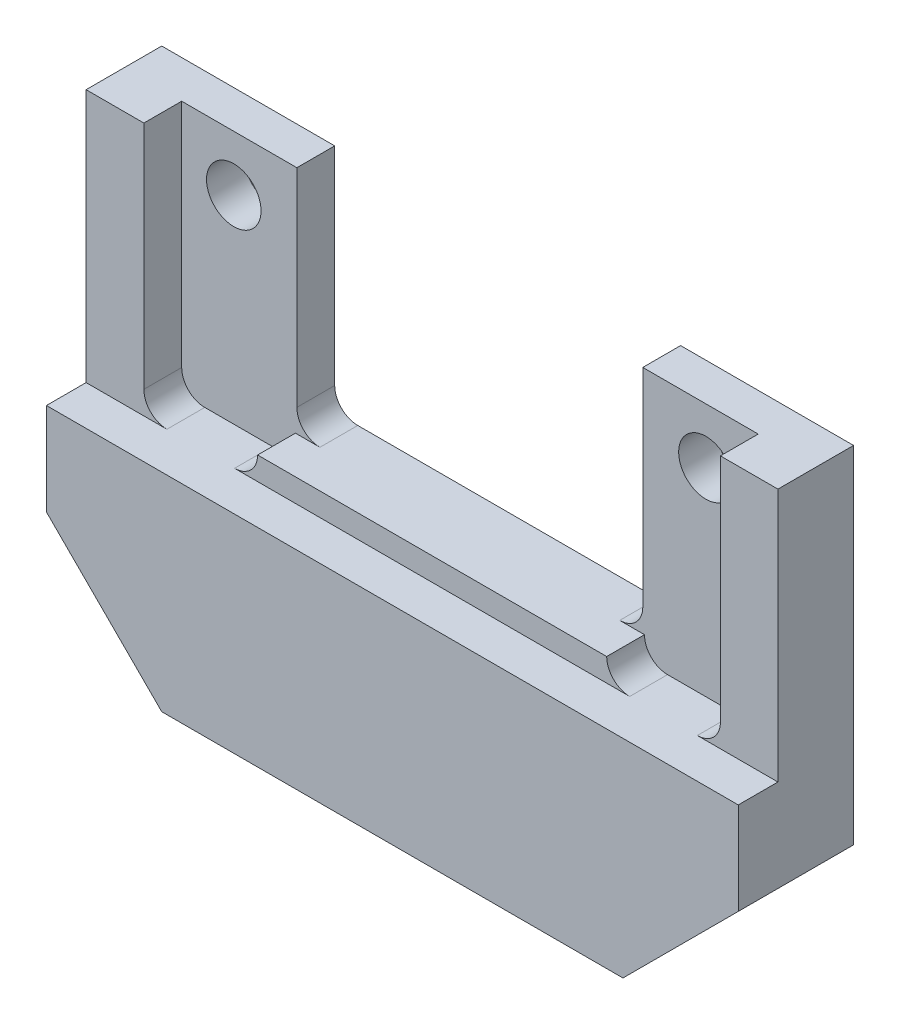
SolidWorks part; units mm, degrees
ref_plane "Front Plane" through (0, 0, 0) normal (0, 0, 1) x (1, 0, 0)
ref_plane "Top Plane" through (0, 0, 0) normal (0, 1, 0) x (1, 0, 0)
ref_plane "Right Plane" through (0, 0, 0) normal (1, 0, 0) x (0, 0, -1)
sketch "Sketch1" plane through (0, 0, 0) normal (0, 0, 1) x (1, 0, 0)
  line L0 (0, 0) -> (0, -16.9661) construction
  line L1 (-19.05, 12.7) -> (19.05, 12.7)
  line L2 (-19.05, 12.7) -> (-19.05, -12.7)
  line L3 (-19.05, -12.7) -> (19.05, -12.7)
  line L4 (19.05, 12.7) -> (19.05, -12.7)
  line L5 (-19.05, 12.7) -> (19.05, -12.7) construction
  line L6 (-19.05, -12.7) -> (19.05, 12.7) construction
  point P0 (0, 0)
  point P7 (-33.8633, 10.3236)
  dimension "D1" = 38.1
  dimension "D2" = 25.4
  dimension "D3" = 19.05
extrude "Boss-Extrude1" add sketch "Sketch1" against normal blind 6.35
sketch "Sketch3" plane through (0, 0, 0) normal (0, 0, 1) x (1, 0, 0)
  line L0 (19.05, -12.7) -> (19.05, 12.7) construction
  line L1 (-19.05, 12.7) -> (19.05, 12.7)
  line L2 (-19.05, 12.7) -> (-19.05, -1.27)
  line L3 (-19.05, -1.27) -> (19.05, -1.27)
  line L4 (19.05, 12.7) -> (19.05, -1.27)
  line L5 (-19.05, 12.7) -> (-19.05, -12.7) construction
  line L6 (0, 17.7648) -> (0, -20.9902) construction
  point P10 (-43.7613, 7.8871)
  dimension "D1" = 13.97
extrude "Cut-Extrude1" cut sketch "Sketch3" against normal blind 2.1844
sketch "Sketch4" plane through (0, 0, -2.1844) normal (0, 0, 1) x (1, 0, 0)
  line L0 (0, 12.7) -> (0, -1.27) construction
  line L1 (19.05, 12.7) -> (-19.05, 12.7) construction
  line L2 (-19.05, -1.27) -> (19.05, -1.27) construction
  circle A0 centre (-13, 9.652) radius 1.27
  circle A1 centre (13, 9.652) radius 1.27
  dimension "D1" = 2.54
  dimension "D2" = 13
  dimension "D3" = 3.048
extrude "Cut-Extrude2" cut sketch "Sketch4" against normal through all
sketch "Sketch5" plane through (0, 0, -2.1844) normal (0, 0, 1) x (1, 0, 0)
  line L1 (-9.4833, -6.35) -> (9.4833, -6.35)
  line L2 (-9.4833, -6.35) -> (-9.4833, 12.7)
  line L3 (-9.4833, 12.7) -> (9.4833, 12.7)
  line L4 (9.4833, -6.35) -> (9.4833, 12.7)
  line L5 (-9.4833, -6.35) -> (9.4833, 12.7) construction
  line L6 (-9.4833, 12.7) -> (9.4833, -6.35) construction
  line L7 (19.05, 12.7) -> (-19.05, 12.7) construction
  point P0 (0, 3.175)
  dimension "D1" = 18.9666
  dimension "D2" = 19.05
extrude "Cut-Extrude4" [suppressed] cut sketch "Sketch5" against normal through all
sketch "Sketch6" plane through (0, 0, 0) normal (0, 0, 1) x (1, 0, 0)
  line L0 (-9.525, 0) -> (9.525, 0)
  line L1 (-9.525, 0) -> (-9.525, 19.05)
  line L2 (-9.525, 19.05) -> (9.525, 19.05)
  line L3 (9.525, 0) -> (9.525, 19.05)
  line L4 (-9.525, 0) -> (9.525, 19.05) construction
  line L5 (-9.525, 19.05) -> (9.525, 0) construction
  line L6 (-19.05, -1.27) -> (-19.05, -12.7) construction
  line L7 (0, 12.7) -> (0, -12.7) construction
  line L8 (19.05, 12.7) -> (-19.05, 12.7) construction
  line L9 (-19.05, -12.7) -> (19.05, -12.7) construction
  line L10 (-19.05, -1.27) -> (19.05, -1.27) construction
  point P0 (0, 9.525)
  dimension "D1" = 12.7
  dimension "D2" = 6.35
  dimension "D3" = 19.05
extrude "Cut-Extrude5" cut sketch "Sketch6" against normal through all
sketch "Sketch7" plane through (0, 12.7, 0) normal (0, 1, 0) x (1, 0, 0)
  line L0 (-19.05, 4.2672) -> (19.05, 4.2672) construction
  line L1 (-9.525, 2.1844) -> (-19.05, 2.1844) construction
  line L3 (0.0069, 0) -> (0.0069, 6.35) construction
  line L5 (15.8819, 4.2672) -> (-15.8681, 4.2672)
  line L6 (15.8819, 4.2672) -> (15.8819, 2.1844)
  line L7 (-15.8681, 4.2672) -> (-15.8681, 2.1844)
  line L8 (15.8819, 2.1844) -> (-15.8681, 2.1844)
  line L9 (15.8819, 4.2672) -> (-15.8681, 2.1844) construction
  line L10 (-15.8681, 4.2672) -> (15.8819, 2.1844) construction
  line L12 (19.05, 2.1844) -> (9.525, 2.1844) construction
  point P4 (20.4607, 9.8114)
  point P8 (20.7708, 8.3058)
  point P10 (27.6032, -2.5649)
  point P12 (0.0069, 3.2258)
  dimension "D1" = 15.875
  dimension "D2" = 15.875
extrude "Cut-Extrude6" cut sketch "Sketch7" against normal blind 12.7
sketch "Sketch8" plane through (0, 0, -6.35) normal (0, 0, -1) x (-1, 0, 0)
  line L0 (19.05, 12.7) -> (19.05, -12.7) construction
  line L1 (-19.05, -12.7) -> (19.05, -12.7)
  line L2 (-19.05, -12.7) -> (-19.05, 0)
  line L3 (-19.05, 0) -> (19.05, 0)
  line L4 (19.05, -12.7) -> (19.05, 0)
extrude "Cut-Extrude7" [suppressed] cut sketch "Sketch8" against normal blind 5.08
chamfer "Chamfer1" [suppressed] distance 0.381 angle 75
chamfer "Chamfer2" [suppressed] distance 0.635 distance2 3.81
chamfer "Chamfer3" [suppressed] distance 3.81 angle 45
chamfer "Chamfer4" [suppressed] distance 3.81 angle 45
sketch "Sketch9" plane through (0, 0, 0) normal (0, 0, 1) x (1, 0, 0)
  line L0 (-19.05, -6.35) -> (19.05, -6.35) construction
  line L1 (-19.05, -1.27) -> (-19.05, -12.7) construction
  line L2 (19.05, -12.7) -> (19.05, -1.27) construction
  line L5 (-19.05, -12.7) -> (19.05, -12.7) construction
  circle A0 centre (0, -6.35) radius 3.2639
  dimension "D2" = 6.5278
  dimension "D1" = 6.35
extrude "Cut-Extrude8" [suppressed] cut sketch "Sketch9" against normal through all
fillet "Fillet1" [suppressed] radius 2.54
fillet "Fillet2" [suppressed] radius 2.54
fillet "Fillet3" [suppressed] radius 10.16
fillet "Fillet5" [suppressed] radius 0.635
chamfer "Chamfer5" [suppressed] distance 1.27 angle 45
fillet "Fillet6" [suppressed] radius 12.7
sketch "Sketch10" plane through (0, 0, -2.1844) normal (0, 0, 1) x (1, 0, 0)
  line L0 (0, 0) -> (0, 27.174) construction
  line L1 (-9.525, 0) -> (9.525, 0) construction
  circle A0 centre (-13, 9.652) radius 1.5
  circle A1 centre (13, 9.652) radius 1.5
  dimension "D1" = 3
extrude "Cut-Extrude9" cut sketch "Sketch10" against normal up to next
chamfer "Chamfer6" [suppressed] distance 5.08 angle 45
chamfer "Chamfer7" [suppressed] distance 3.81 angle 45
chamfer "Chamfer8" [suppressed] distance 2.54 angle 45
chamfer "Chamfer9" [suppressed] distance 2.54 angle 45
sketch "Sketch15" plane through (0, 0, 0) normal (0, 1, 0) x (1, 0, 0)
  line L0 (-15.8681, 4.2672) -> (-15.8681, 2.1844)
  line L1 (-15.8681, 4.2672) -> (-9.6048, 4.2672)
  line L2 (-15.8681, 2.1844) -> (-9.6048, 2.1844)
  line L3 (-9.6048, 4.2672) -> (-9.6048, 2.1844)
  line L4 (0.0069, 0) -> (0.0069, 9.0818) construction
  line L5 (15.8819, 2.1844) -> (9.6185, 2.1844)
  line L6 (15.8819, 4.2672) -> (15.8819, 2.1844)
  line L7 (15.8819, 4.2672) -> (9.6185, 4.2672)
  line L8 (9.6185, 4.2672) -> (9.6185, 2.1844)
  dimension "D1" = 15.875
extrude "Cut-Extrude14" cut sketch "Sketch15" against normal blind 1.27
fillet "Fillet7" radius 1.27 6 edges at (15.8819, -1.27, -3.2258) (-15.8681, -1.27, -3.2258) (-9.525, 0, -5.3086) (9.525, 0, -5.3086) (-9.6048, -1.27, -3.2258) (9.6185, -1.27, -3.2258)
chamfer "Chamfer10" distance 6.35 angle 45 2 edges at (-19.05, -12.7, -3.175) (19.05, -12.7, -3.175)
sketch "Sketch14" [suppressed] plane through (0, 0, 0) normal (0, 1, 0) x (1, 0, 0)
  line L0 (0, -1.0462) -> (0, 7.8572) construction
  line L1 (-9.525, 4.2672) -> (-15.8681, 4.2672)
  line L2 (-9.525, 4.2672) -> (-9.525, 2.1844)
  line L3 (-9.525, 2.1844) -> (-15.8681, 2.1844)
  line L4 (-15.8681, 4.2672) -> (-15.8681, 2.1844)
  line L5 (15.8681, 4.2672) -> (15.8681, 2.1844)
  line L6 (9.525, 4.2672) -> (15.8681, 4.2672)
  line L7 (9.525, 2.1844) -> (15.8681, 2.1844)
  line L8 (9.525, 4.2672) -> (9.525, 2.1844)
extrude "Cut-Extrude13" [suppressed] cut sketch "Sketch14" against normal blind 1.27
sketch "Sketch17" plane through (-12.7, -12.7, 0) normal (-0.7071, -0.7071, 0) x (0, 0, 1)
  line L0 (0, 4.4901) -> (-6.35, 4.4901) construction
  line L1 (0, 8.9803) -> (0, 0) construction
  line L2 (-6.35, 0) -> (-6.35, 8.9803) construction
  line L3 (-3.175, 8.9803) -> (-3.175, 0) construction
  line L4 (-6.35, 8.9803) -> (0, 8.9803) construction
  line L5 (0, 0) -> (-6.35, 0) construction
  point P12 (-3.175, 4.4901)
sketch "Sketch18" plane through (12.7, -12.7, 0) normal (0.7071, -0.7071, 0) x (0, 0, -1)
  line L0 (0, 4.4901) -> (6.35, 4.4901) construction
  line L1 (0, 0) -> (0, 8.9803) construction
  line L2 (6.35, 8.9803) -> (6.35, 0) construction
  line L3 (3.175, 0) -> (3.175, 8.9803) construction
  line L4 (6.35, 0) -> (0, 0) construction
  line L5 (0, 8.9803) -> (6.35, 8.9803) construction
  point P12 (3.175, 4.4901)
hole_wizard "#8-32 Tapped Hole2" positions "Sketch20" profile "Sketch19" tap size "#8-32" standard "ANSI Inch"
sketch "Sketch20" plane through (-12.7, -12.7, 0) normal (-0.7071, -0.7071, 0) x (-0.7071, 0.7071, 0)
  point P0 (4.4901, 3.175)
sketch "Sketch19" plane through (-15.875, -9.525, -3.175) normal (0, 0, 1) x (0.7071, -0.7071, 0)
  line L0 (0, 0) -> (0, 7.3878)
  line L1 (0, 7.3878) -> (1.7272, 6.35)
  line L2 (1.7272, 6.35) -> (1.7272, 0.8128)
  line L3 (1.7272, 0.8128) -> (2.54, 0)
  line L5 (2.54, 0) -> (0, 0)
  line L6 (-1.7272, 0.8128) -> (-2.54, 0) construction
  line L10 (0, 7.3878) -> (-1.7272, 6.35) construction
  line L11 (0, -6.35) -> (0, 107.95) construction
  dimension "Tap Drill Dia." = 3.4544
  dimension "Tap Drill Depth" = 6.35
  dimension "Near C'Sink Dia." = 5.08
  dimension "Near C'Sink Angle" = 90
  dimension "Drill Angle" = 118
hole_wizard "#8-32 Tapped Hole3" positions "Sketch22" profile "Sketch21" tap size "#8-32" standard "ANSI Inch"
sketch "Sketch22" plane through (12.7, -12.7, 0) normal (0.7071, -0.7071, 0) x (0, 0, -1)
  point P0 (3.175, 4.4901)
sketch "Sketch21" plane through (15.875, -9.525, -3.175) normal (0, 0, 1) x (0.7071, 0.7071, 0)
  line L0 (0, 0) -> (0, 7.3878)
  line L1 (0, 7.3878) -> (1.7272, 6.35)
  line L2 (1.7272, 6.35) -> (1.7272, 0.8128)
  line L3 (1.7272, 0.8128) -> (2.54, 0)
  line L5 (2.54, 0) -> (0, 0)
  line L6 (-1.7272, 0.8128) -> (-2.54, 0) construction
  line L10 (0, 7.3878) -> (-1.7272, 6.35) construction
  line L11 (0, -6.35) -> (0, 107.95) construction
  dimension "Tap Drill Dia." = 3.4544
  dimension "Tap Drill Depth" = 6.35
  dimension "Near C'Sink Dia." = 5.08
  dimension "Near C'Sink Angle" = 90
  dimension "Drill Angle" = 118
